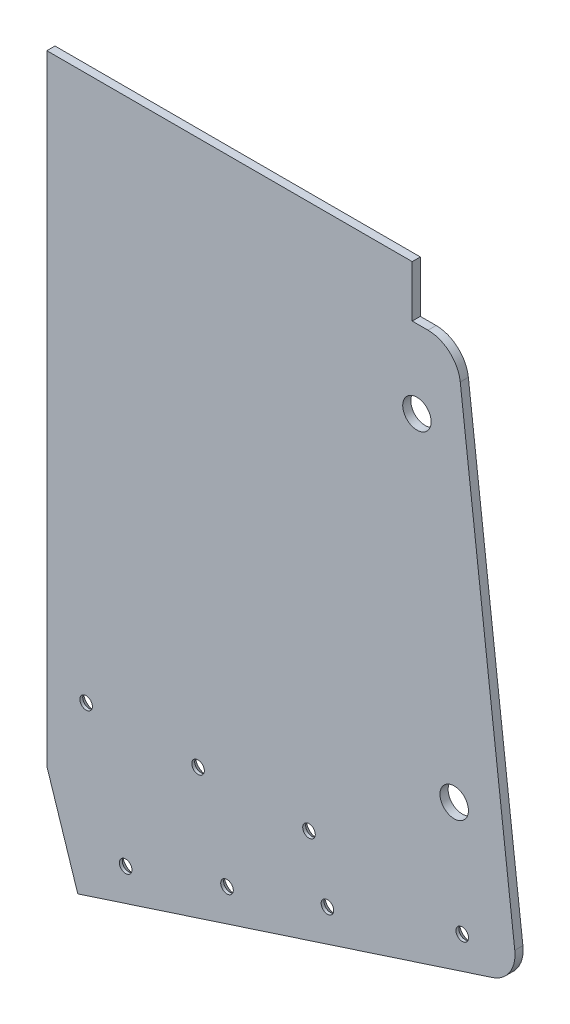
SolidWorks part; units mm, degrees
material "Acrylic (Medium-high impact)"
ref_plane "Front Plane" through (0, 0, 0) normal (0, 0, 1) x (1, 0, 0)
ref_plane "Top Plane" through (0, 0, 0) normal (0, 1, 0) x (1, 0, 0)
ref_plane "Right Plane" through (0, 0, 0) normal (1, 0, 0) x (0, 0, -1)
sketch "Sketch1" plane through (0, 0, 0) normal (0, 0, 1) x (1, 0, 0)
  line L1 (-234.753, 12.7) -> (-91.9973, 12.7)
  line L2 (-234.753, 12.7) -> (-234.753, -270.5428)
  line L3 (-234.753, -270.5428) -> (-50.7003, -210.6746)
  line L4 (-74.5335, -7.417) -> (-50.7003, -210.6746)
  line L5 (-64.9774, -197.966) -> (-88.1902, 0) construction
  line L8 (-74.5335, -7.417) -> (-91.9973, -7.417)
  line L9 (-91.9973, -7.417) -> (-91.9973, 12.7)
  line L10 (-91.9973, 0) -> (-91.9973, 12.7) construction
  dimension "D1" = 12.7
  dimension "D2" = 71.981
  dimension "D3" = 283.2428
extrude "Boss-Extrude1" add sketch "Sketch1" along normal blind 3.175
fillet "Fillet1" radius 12.7 2 edges at (-74.5335, -7.417, 1.5875) (-50.7003, -210.6746, 1.5875)
sketch "Sketch2" plane through (0, 0, 3.175) normal (0, 0, 1) x (1, 0, 0)
  line L0 (-234.753, -270.5428) -> (-60.5975, -213.8939) construction
  line L1 (-234.753, 12.7) -> (-234.753, -270.5428) construction
  line L2 (-234.753, -270.5428) -> (-222.6758, -266.6143)
  line L3 (-234.753, -229.4856) -> (-234.753, -270.5428)
  line L4 (-222.6758, -266.6143) -> (-234.753, -229.4856)
  dimension "D1" = 12.7
extrude "Cut-Extrude1" cut sketch "Sketch2" against normal through all
hole_wizard "CSK for #8 Flat Head Machine Screw1" positions "Sketch3" profile "Sketch4" countersink size "#8" standard "ANSI Inch" end condition through all
sketch "Sketch3" plane through (0, 0, 0) normal (0, 0, -1) x (-1, 0, 0)
  point P0 (203.9698, -247.917)
  point P3 (164.3688, -235.0357)
  point P6 (175.687, -200.2402)
  point P9 (219.4388, -200.3608)
  point P12 (125.1181, -222.2683)
  point P15 (132.3222, -200.1207)
  point P18 (72.4521, -205.1373)
sketch "Sketch4" plane through (-203.9698, -247.917, 0) normal (1, 0, 0) x (0, 1, 0)
  line L0 (0, 0) -> (0, 3.175)
  line L1 (0, 3.175) -> (2.4574, 3.175)
  line L2 (2.4574, 3.175) -> (2.4574, 2.0234)
  line L3 (2.4574, 2.0234) -> (4.2164, 0)
  line L5 (4.2164, 0) -> (0, 0)
  line L6 (-2.4574, 2.0234) -> (-4.2164, 0) construction
  line L11 (0, -6.35) -> (0, 107.95) construction
  dimension "Thru Hole Dia." = 4.9149
  dimension "Thru Hole Depth" = 3.175
  dimension "Near C'Sink Dia." = 8.4328
  dimension "Near C'Sink Angle" = 82
sketch "Sketch5" plane through (0, 0, 3.175) normal (0, 0, 1) x (1, 0, 0)
  circle A0 centre (-90.1466, -37.8408) radius 5.5563
  circle A1 centre (-75.5767, -162.098) radius 5.5563
  point P2 (0, 0)
  point P5 (-87.4064, -142.7745)
  point P6 (-75.5767, -162.098)
  point P7 (0, 0)
  dimension "D1" = 11.1125
extrude "Cut-Extrude2" cut sketch "Sketch5" against normal up to next
